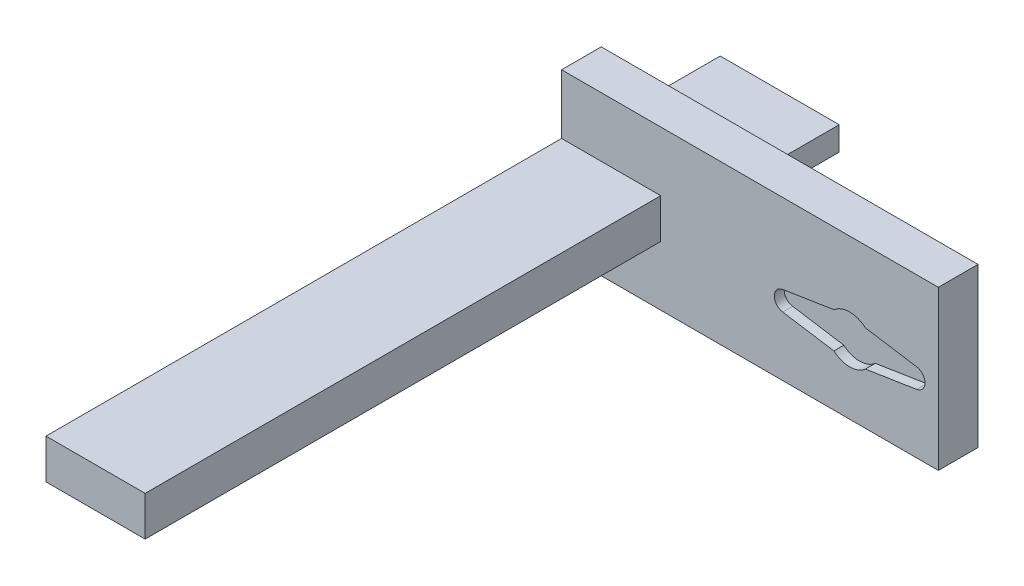
SolidWorks part; units mm, degrees
ref_plane "Front Plane" through (0, 0, 0) normal (0, 0, 1) x (1, 0, 0)
ref_plane "Top Plane" through (0, 0, 0) normal (0, 1, 0) x (1, 0, 0)
ref_plane "Right Plane" through (0, 0, 0) normal (1, 0, 0) x (0, 0, -1)
sketch "Sketch3" plane through (0, 0, 0) normal (0, 0, 1) x (1, 0, 0)
  line L1 (-22.6388, -7.4411) -> (22.3612, -7.4411)
  line L2 (-22.6388, -7.4411) -> (-22.6388, 7.5589)
  line L3 (-22.6388, 7.5589) -> (22.3612, 7.5589)
  line L4 (22.3612, -7.4411) -> (22.3612, 7.5589)
  dimension "D1" = 15
  dimension "D2" = 45
extrude "Boss-Extrude1" add sketch "Sketch3" against normal blind 10
sketch "Sketch2" plane through (0, 0, 0) normal (0, 0, 1) x (1, 0, 0)
  line L0 (-16.8881, 2.4697) -> (-3.9686, 4.5)
  line L1 (-16.8881, -2.4697) -> (-3.9686, -4.5)
  line L2 (3.9686, 4.5) -> (16.8881, 2.4697)
  line L3 (16.8881, -2.4697) -> (3.9686, -4.5)
  arc A0 (-16.8881, 2.4697) -> (-16.8881, -2.4697) centre (-16.5, 0) ccw
  arc A1 (-3.9686, 4.5) -> (3.9686, 4.5) centre (0, 0) cw
  arc A2 (-3.9686, -4.5) -> (3.9686, -4.5) centre (0, 0) ccw
  arc A3 (16.8881, -2.4697) -> (16.8881, 2.4697) centre (16.5, 0) ccw
extrude "Cut-Extrude1" cut sketch "Sketch2" against normal blind 2.5
sketch "Sketch11" plane through (0, -7.4411, 0) normal (0, -1, 0) x (1, 0, 0)
  line L0 (8.25, 0) -> (-8.25, 0) construction
  line L1 (22.3612, -10) -> (-22.6388, -10)
  line L2 (22.3612, -10) -> (22.3612, 0)
  line L3 (22.3612, 0) -> (-22.6388, 0)
  line L4 (-22.6388, -10) -> (-22.6388, 0)
  line L5 (-22.6388, -10) -> (-22.6388, 0) construction
extrude "Boss-Extrude5" add sketch "Sketch11" along normal blind 10
sketch "Sketch14" plane through (0, 7.5589, 0) normal (0, 1, 0) x (1, 0, 0)
  line L0 (-8.25, 0) -> (8.25, 0) construction
  line L1 (22.3612, 10) -> (-22.6388, 10)
  line L2 (22.3612, 10) -> (22.3612, 0)
  line L3 (22.3612, 0) -> (-22.6388, 0)
  line L4 (-22.6388, 10) -> (-22.6388, 0)
  line L5 (-22.6388, 10) -> (-22.6388, 0) construction
extrude "Boss-Extrude7" add sketch "Sketch14" along normal blind 15
sketch "Sketch20" plane through (-22.6388, 0, 0) normal (-1, 0, 0) x (0, 0, 1)
  line L0 (0, -22) -> (0, 22) construction
  line L1 (-10, 22.5589) -> (0, 22.5589)
  line L2 (-10, 22.5589) -> (-10, -17.4411)
  line L3 (-10, -17.4411) -> (0, -17.4411)
  line L4 (0, 22.5589) -> (0, -17.4411)
  line L5 (0, -17.4411) -> (-10, -17.4411) construction
extrude "Boss-Extrude10" add sketch "Sketch20" along normal blind 50
sketch "Sketch21" plane through (0, 0, 0) normal (0, 0, 1) x (1, 0, 0)
  line L0 (-72.6388, -17.4411) -> (-72.6388, 22.5589) construction
  line L1 (-72.6388, 7.5589) -> (-47.6388, 7.5589)
  line L2 (-72.6388, 7.5589) -> (-72.6388, -2.4411)
  line L3 (-72.6388, -2.4411) -> (-47.6388, -2.4411)
  line L4 (-47.6388, 7.5589) -> (-47.6388, -2.4411)
  line L5 (-72.6388, 22.5589) -> (22.3612, 22.5589) construction
  dimension "D1" = 25
  dimension "D2" = 10
  dimension "D3" = 15
extrude "Boss-Extrude11" add sketch "Sketch21" along normal blind 130
sketch "Sketch22" plane through (0, 0, -10) normal (0, 0, -1) x (-1, 0, 0)
  line L0 (72.6388, 22.5589) -> (72.6388, -17.4411) construction
  line L1 (42.6388, 5.5589) -> (72.6388, 5.5589)
  line L2 (42.6388, 5.5589) -> (42.6388, -0.4411)
  line L3 (42.6388, -0.4411) -> (72.6388, -0.4411)
  line L4 (72.6388, 5.5589) -> (72.6388, -0.4411)
  line L5 (42.6388, 5.5589) -> (72.6388, -0.4411) construction
  line L6 (42.6388, -0.4411) -> (72.6388, 5.5589) construction
  line L7 (72.6388, -17.4411) -> (-22.3612, -17.4411) construction
  point P0 (57.6388, 2.5589)
  dimension "D1" = 20
  dimension "D2" = 30
  dimension "D3" = 6
extrude "Boss-Extrude12" add sketch "Sketch22" along normal blind 30
